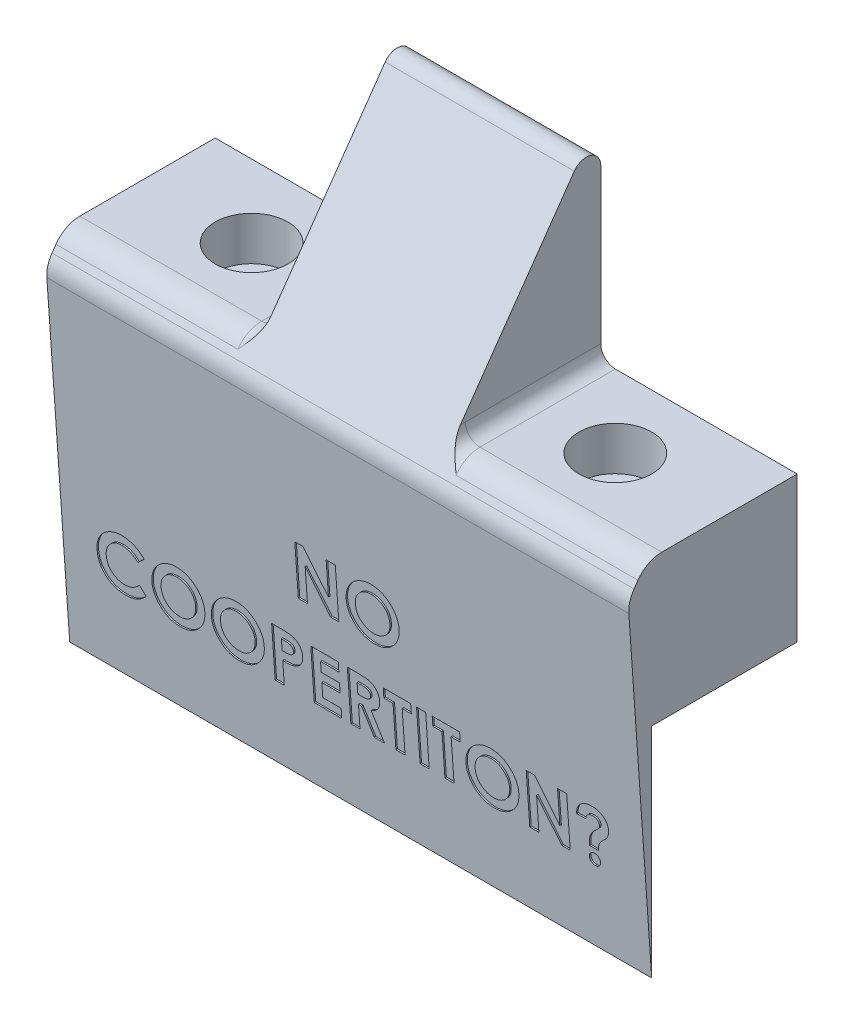
SolidWorks part; units mm, degrees
ref_plane "Front Plane" through (0, 0, 0) normal (0, 0, 1) x (1, 0, 0)
ref_plane "Top Plane" through (0, 0, 0) normal (0, 1, 0) x (1, 0, 0)
ref_plane "Right Plane" through (0, 0, 0) normal (1, 0, 0) x (0, 0, -1)
sketch "Sketch2" plane through (0, 0, 0) normal (0, 1, 0) x (1, 0, 0)
  line L1 (-50.8, 15.24) -> (50.8, 15.24)
  line L2 (-50.8, 15.24) -> (-50.8, -15.24)
  line L3 (-50.8, -15.24) -> (50.8, -15.24)
  line L4 (50.8, 15.24) -> (50.8, -15.24)
  line L5 (-50.8, 15.24) -> (50.8, -15.24) construction
  line L6 (-50.8, -15.24) -> (50.8, 15.24) construction
  point P0 (0, 0)
  dimension "D1" = 101.6
  dimension "D2" = 30.48
extrude "Boss-Extrude1" add sketch "Sketch2" along normal blind 63.5
sketch "Sketch3" plane through (0, 0, 0) normal (0, -1, 0) x (-1, 0, 0)
  line L0 (50.8, 15.24) -> (50.8, -15.24) construction
  line L1 (-50.8, 15.24) -> (50.8, 15.24)
  line L2 (-50.8, 15.24) -> (-50.8, -10.16)
  line L3 (-50.8, -10.16) -> (50.8, -10.16)
  line L4 (50.8, 15.24) -> (50.8, -10.16)
  dimension "D1" = 25.4
extrude "Cut-Extrude1" cut sketch "Sketch3" against normal blind 38.1
chamfer "Chamfer1" distance 5.08 angle 86 1 edges at (0, 0, 15.24) first distance on face at (0, 0, 12.7)
chamfer "Chamfer2" [suppressed] distance 12.7 angle 35
fillet "Fillet1" [suppressed] radius 11.43
fillet "Fillet2" [suppressed] radius 11.43
sketch "Sketch4" plane through (0, 63.5, 0) normal (0, 1, 0) x (1, 0, 0)
  line L0 (50.8, -14.6004) -> (50.8, 15.24) construction
  line L1 (-50.8, 15.24) -> (-50.8, -14.6004) construction
  line L2 (50.8, 15.24) -> (-50.8, 15.24) construction
  circle A0 centre (-31.75, 2.54) radius 3.429
  circle A1 centre (31.75, 2.54) radius 3.429
  dimension "D1" = 6.858
  dimension "D2" = 6.858
  dimension "D3" = 19.05
  dimension "D4" = 19.05
  dimension "D5" = 12.7
  dimension "D6" = 12.7
extrude "Cut-Extrude2" cut sketch "Sketch4" against normal through all
sketch "Sketch5" plane through (0, 63.5, 0) normal (0, 1, 0) x (1, 0, 0)
  circle A0 centre (-31.75, 2.54) radius 6.35
  circle A1 centre (31.75, 2.54) radius 6.35
  dimension "D1" = 12.7
  dimension "D2" = 12.7
extrude "Cut-Extrude3" cut sketch "Sketch5" against normal blind 7.62
sketch "Sketch6" plane through (0, 63.5, 0) normal (0, 1, 0) x (1, 0, 0)
  line L0 (50.8, 15.24) -> (-50.8, 15.24) construction
  line L1 (-16.51, 15.24) -> (16.51, 15.24)
  line L2 (-16.51, 15.24) -> (-16.51, -14.6004)
  line L3 (-16.51, -14.6004) -> (16.51, -14.6004)
  line L4 (16.51, 15.24) -> (16.51, -14.6004)
  line L5 (-50.8, -14.6004) -> (50.8, -14.6004) construction
  line L6 (-50.8, 15.24) -> (-50.8, -14.6004) construction
  line L7 (50.8, -14.6004) -> (50.8, 15.24) construction
  dimension "D1" = 34.29
  dimension "D2" = 34.29
extrude "Boss-Extrude2" add sketch "Sketch6" along normal blind 38.1
chamfer "Chamfer3" distance 43.18 angle 35 1 edges at (0, 101.6, 14.6004) first distance on face at (0, 82.55, 14.6004)
fillet "Fillet5" radius 5.08 3 edges at (33.655, 63.5, 11.0433) (-33.655, 63.5, 11.0433) (0, 58.8813, 14.2774)
fillet "Fillet6" radius 2.54 1 edges at (0, 101.0364, -15.24)
fillet "Fillet7" radius 2.54 4 edges at (16.51, 62.926, 10.7445) (-16.51, 62.926, 10.7445) (16.51, 63.5, -3.4206) (-16.51, 63.5, -3.4206)
sketch "Sketch7" plane through (0, -0.707, 10.1106) normal (0, -0.0698, 0.9976) x (1, 0, 0)
  line L0 (-50.8, 29.3218) -> (50.8, 29.3218) construction
  line L1 (-50.8, 0.7087) -> (-50.8, 57.9348) construction
  line L2 (50.8, 57.9348) -> (50.8, 0.7087) construction
  text T0 "<b>NO</b>\r\n<b>COOPERTITON?</b>" font "Century Gothic" height 8.89
extrude "Cut-Extrude4" cut sketch "Sketch7" against normal blind 0.254
